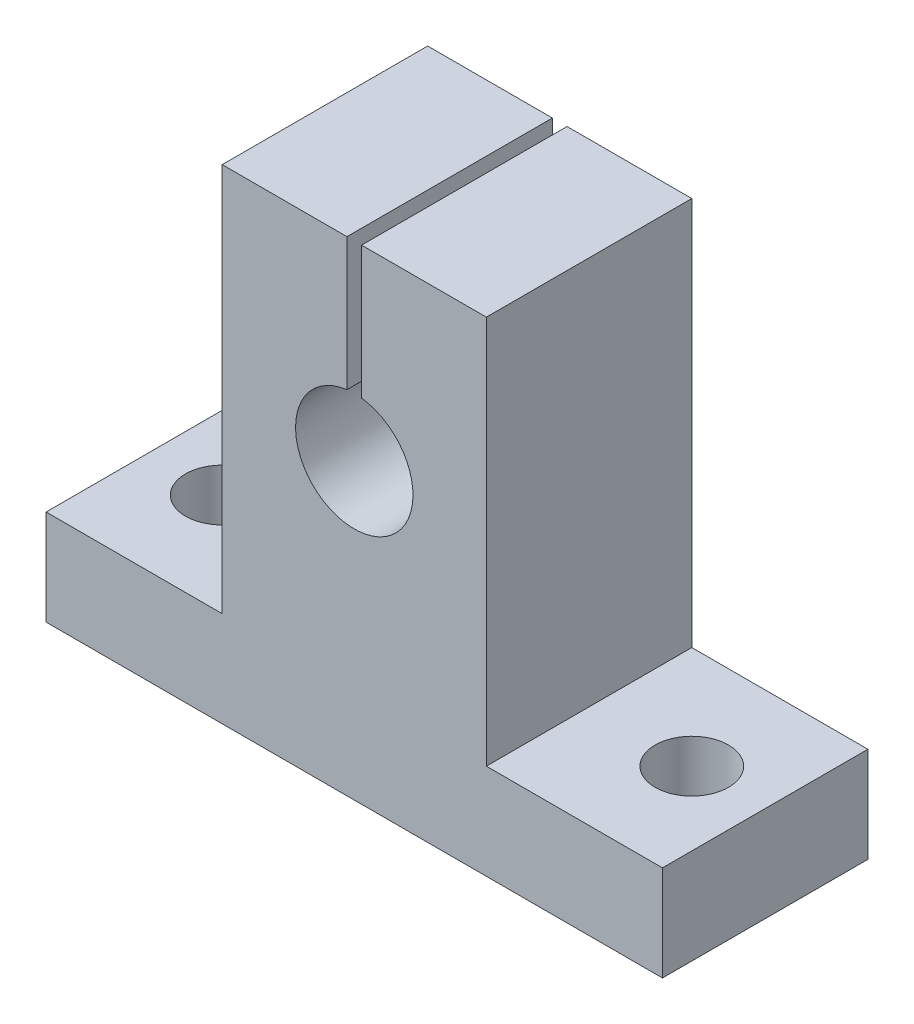
SolidWorks part; units mm, degrees
ref_plane "Front Plane" through (0, 0, 0) normal (0, 0, 1) x (1, 0, 0)
ref_plane "Top Plane" through (0, 0, 0) normal (0, 1, 0) x (1, 0, 0)
ref_plane "Right Plane" through (0, 0, 0) normal (1, 0, 0) x (0, 0, -1)
sketch "Sketch1" plane through (0, 0, 0) normal (0, 0, 1) x (1, 0, 0)
  line L0 (9, 3.25) -> (21, 3.25)
  line L1 (-21, -3.25) -> (21, -3.25)
  line L2 (-21, -3.25) -> (-21, 3.25)
  line L3 (-21, 3.25) -> (-9, 3.25)
  line L4 (21, -3.25) -> (21, 3.25)
  line L5 (-21, -3.25) -> (21, 3.25) construction
  line L6 (-21, 3.25) -> (21, -3.25) construction
  line L7 (-9, 29.75) -> (9, 29.75)
  line L8 (-9, 29.75) -> (-9, 3.25)
  line L10 (9, 29.75) -> (9, 3.25)
  line L11 (-9, 29.75) -> (9, 3.25) construction
  line L12 (-9, 3.25) -> (9, 29.75) construction
  point P0 (0, 0)
  point P6 (0, 16.5)
  dimension "D1" = 42
  dimension "D2" = 6.5
  dimension "D3" = 18
  dimension "D4" = 26.5
extrude "Boss-Extrude1" add sketch "Sketch1" along normal blind 7 and the other way blind 7
sketch "Sketch2" plane through (0, 0, 7) normal (0, 0, 1) x (1, 0, 0)
  line L0 (9, 29.75) -> (-9, 29.75) construction
  line L1 (-0.5, 20.7186) -> (-0.5, 29.75)
  line L4 (-0.5, 29.75) -> (0.5, 29.75)
  line L10 (0.5, 20.7186) -> (0.5, 29.75)
  arc A0 (-0.5, 20.7186) -> (0.5, 20.7186) centre (0, 16.75) ccw
  dimension "D2" = 8
  dimension "D1" = 13
  dimension "D3" = 1
extrude "Cut-Extrude1" cut sketch "Sketch2" against normal through all
sketch "Sketch3" plane through (0, 3.25, 0) normal (0, 1, 0) x (1, 0, 0)
  line L0 (21, 7) -> (21, -7) construction
  line L1 (21, -7) -> (9, -7) construction
  line L2 (0, -7.7) -> (0, 7.7) construction
  circle A0 centre (16, 0) radius 2.5
  circle A1 centre (-16, 0) radius 2.5
  dimension "D3" = 5
  dimension "D1" = 5
  dimension "D2" = 7
extrude "Cut-Extrude2" cut sketch "Sketch3" against normal through all
